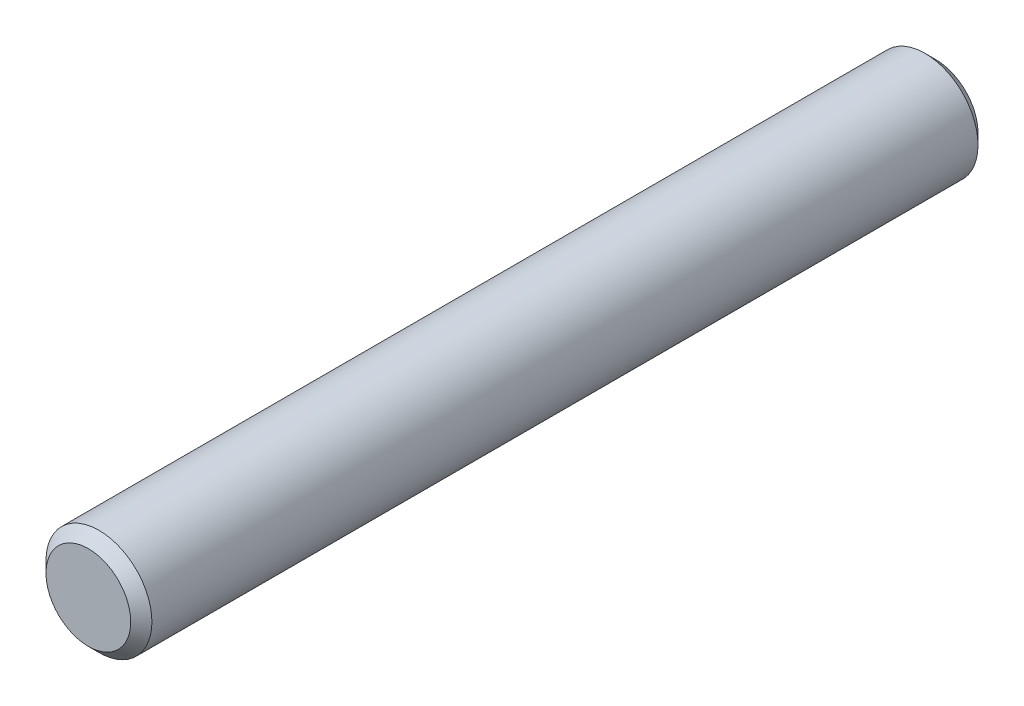
SolidWorks part; units mm, degrees
ref_plane "Ebene vorne" through (0, 0, 0) normal (0, 0, 1) x (1, 0, 0)
ref_plane "Ebene oben" through (0, 0, 0) normal (0, 1, 0) x (1, 0, 0)
ref_plane "Ebene rechts" through (0, 0, 0) normal (1, 0, 0) x (0, 0, -1)
sketch "Skizze1" plane through (0, 0, 0) normal (0, 0, 1) x (1, 0, 0)
  circle A0 centre (0, 0) radius 1
  dimension "D1" = 2
extrude "Aufsatz-Linear austragen1" add sketch "Skizze1" along normal blind 8 and the other way blind 8
ref_axis "Achse1" through (0, 0, -8.8) along (0, 0, 1)
chamfer "Fase1" distance 0.2 angle 45 2 edges at (1, 0, -8) (1, 0, 8)
